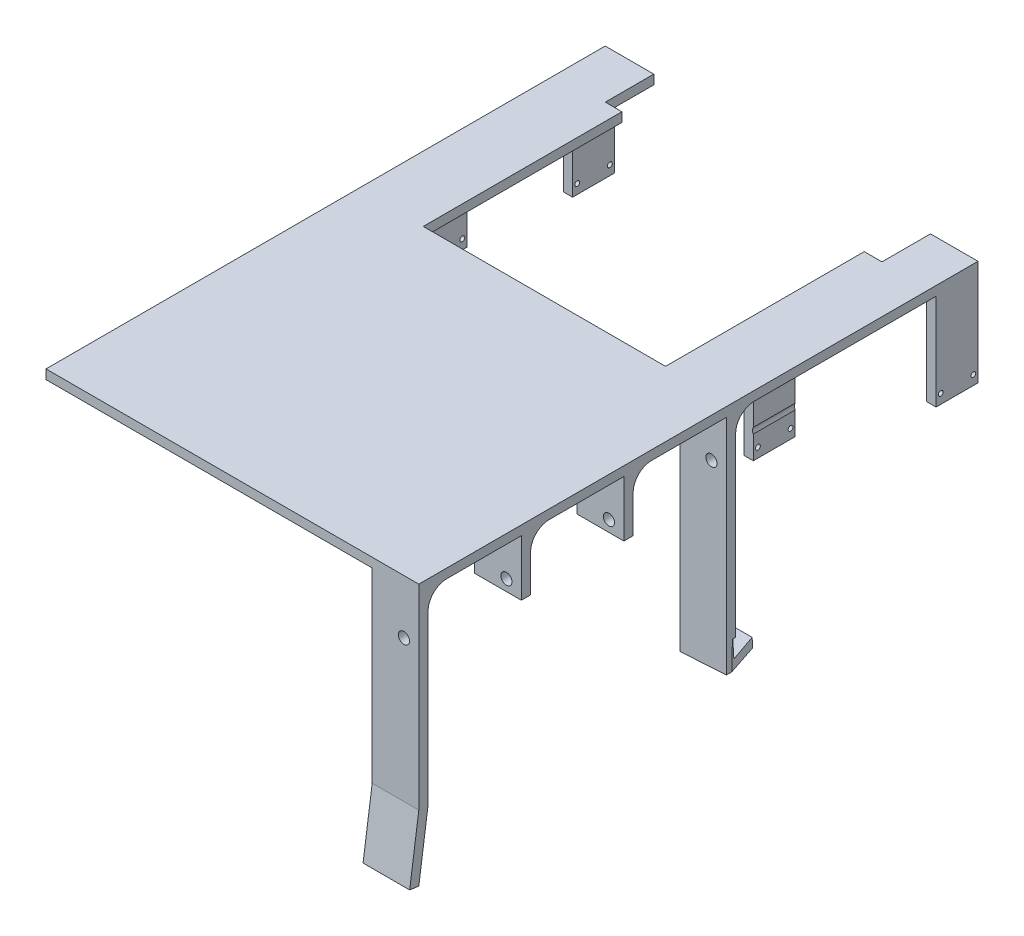
SolidWorks part; units mm, degrees
ref_plane "Front Plane" through (0, 0, 0) normal (0, 0, 1) x (1, 0, 0)
ref_plane "Top Plane" through (0, 0, 0) normal (0, 1, 0) x (1, 0, 0)
ref_plane "Right Plane" through (0, 0, 0) normal (1, 0, 0) x (0, 0, -1)
sketch "Sketch1" plane through (0, 0, 0) normal (0, 1, 0) x (1, 0, 0)
  line L0 (0, 0) -> (0, -300)
  line L1 (0, -300) -> (200, -300)
  line L2 (200, -300) -> (200, 0)
  line L3 (200, 0) -> (190, 0)
  line L4 (190, 0) -> (165, 0)
  line L5 (165, 0) -> (165, -132.6267)
  line L6 (165, -132.6267) -> (35, -132.6267)
  line L7 (35, -132.6267) -> (35, 0)
  line L8 (35, 0) -> (10, 0)
  line L9 (10, 0) -> (0, 0)
  line L10 (100, -300) -> (100, -132.6267) construction
  point P9 (100, -132.6267)
  point P12 (120, 0)
  dimension "D1" = 300
  dimension "D2" = 10
  dimension "D3" = 200
  dimension "D5" = 10
  dimension "D6" = 35
extrude "Boss-Extrude1" add sketch "Sketch1" along normal blind 5
sketch "Sketch2" plane through (0, 0, 0) normal (0, -1, 0) x (1, 0, 0)
  line L1 (8.3629, 110) -> (13.3629, 110)
  line L2 (8.3629, 110) -> (8.3629, 87.5)
  line L3 (8.3629, 87.5) -> (13.3629, 87.5)
  line L4 (13.3629, 110) -> (13.3629, 87.5)
  line L6 (189.4438, 110) -> (184.4438, 110)
  line L7 (189.4438, 110) -> (189.4438, 87.5)
  line L8 (189.4438, 87.5) -> (184.4438, 87.5)
  line L9 (184.4438, 110) -> (184.4438, 87.5)
  line L10 (0, 300) -> (200, 300) construction
  dimension "D1" = 5
  dimension "D2" = 22.5
  dimension "D3" = 5
  dimension "D4" = 190
  dimension "D5" = 22.5
extrude "Boss-Extrude2" add sketch "Sketch2" along normal blind 38
sketch "Sketch5" plane through (0, 0, 0) normal (0, -1, 0) x (1, 0, 0)
  line L0 (200, 300) -> (200, 0) construction
  line L1 (200, 295) -> (175, 295)
  line L2 (200, 295) -> (200, 300)
  line L3 (200, 300) -> (175, 300)
  line L4 (175, 295) -> (175, 300)
  line L5 (0, 300) -> (200, 300) construction
  line L6 (200, 240) -> (175, 240)
  line L7 (200, 240) -> (200, 245)
  line L8 (200, 245) -> (175, 245)
  line L9 (175, 240) -> (175, 245)
  line L10 (200, 185) -> (175, 185)
  line L11 (200, 185) -> (200, 190)
  line L12 (200, 190) -> (175, 190)
  line L13 (175, 185) -> (175, 190)
  line L14 (200, 130) -> (175, 130)
  line L15 (200, 130) -> (200, 135)
  line L16 (200, 135) -> (175, 135)
  line L17 (175, 130) -> (175, 135)
  dimension "D1" = 5
  dimension "D2" = 5
  dimension "D3" = 5
  dimension "D4" = 5
  dimension "D5" = 50
  dimension "D6" = 50
  dimension "D7" = 50
  dimension "D8" = 25
extrude "Boss-Extrude3" add sketch "Sketch5" along normal blind 30
fillet "Fillet3" radius 10 4 edges at (187.5, 0, 130) (187.5, 0, 185) (187.5, 0, 240) (187.5, 0, 295)
sketch "Sketch6" plane through (0, 0, 300) normal (0, 0, 1) x (1, 0, 0)
  line L0 (200, -30) -> (175, -30) construction
  line L1 (200, 5) -> (200, -30) construction
  circle A0 centre (192, -24) radius 3
  point P2 (0, 0)
  dimension "D1" = 6
  dimension "D2" = 6
  dimension "D3" = 8
extrude "Cut-Extrude4" cut sketch "Sketch6" against normal through all
sketch "Sketch7" plane through (0, 0, 0) normal (0, -1, 0) x (1, 0, 0)
  line L0 (0, 0) -> (0, 300) construction
  line L1 (0, 22.5) -> (5, 22.5)
  line L2 (0, 22.5) -> (0, 0)
  line L3 (0, 0) -> (5, 0)
  line L4 (5, 22.5) -> (5, 0)
  line L6 (200, 22.5) -> (195, 22.5)
  line L7 (200, 22.5) -> (200, 0)
  line L8 (200, 0) -> (195, 0)
  line L9 (195, 22.5) -> (195, 0)
  line L10 (200, 0) -> (165, 0) construction
  dimension "D1" = 5
  dimension "D2" = 5
  dimension "D3" = 22.5
  dimension "D4" = 22.5
extrude "Boss-Extrude4" add sketch "Sketch7" along normal blind 51.5
sketch "Sketch3" plane through (200, 0, 0) normal (1, 0, 0) x (0, 0, -1)
  line L4 (-87.5, 0) -> (-110, 0)
  line L5 (-87.5, -38) -> (-87.5, 0)
  line L6 (-110, -38) -> (-87.5, -38)
  line L7 (-110, 0) -> (-110, -38)
  line L9 (-87.5, -38) -> (-87.5, 0)
  line L10 (-110, -38) -> (-87.5, -38)
  line L11 (-110, 0) -> (-110, -38)
  line L13 (-87.5, 0) -> (-110, 0)
  circle A0 centre (-107.5, -32.9) radius 1.3 construction
  circle A1 centre (-90, -32.9) radius 1.3 construction
  circle A2 centre (-107.5, -32.9) radius 1.3
  circle A3 centre (-90, -32.9) radius 1.3
  circle A4 centre (-20, -46.4) radius 1.3 construction
  circle A5 centre (-2.5, -46.4) radius 1.3 construction
  circle A6 centre (-20, -46.4) radius 1.3
  circle A7 centre (-2.5, -46.4) radius 1.3
  dimension "D1" = 0
extrude "Cut-Extrude2" cut sketch "Sketch3" against normal through all contours A3 | A2 | A6 | A7
sketch "Sketch9" plane through (0, 0, 0) normal (0, -1, 0) x (1, 0, 0)
  line L0 (35, 0) -> (5, 0) construction
  line L1 (26.0812, 0) -> (174.514, 0)
  line L2 (26.0812, 0) -> (26.0812, 26.03)
  line L3 (26.0812, 26.03) -> (174.514, 26.03)
  line L4 (174.514, 0) -> (174.514, 26.03)
extrude "Cut-Extrude6" cut sketch "Sketch9" against normal blind 10
sketch "Sketch10" plane through (0, -30, 0) normal (0, -1, 0) x (1, 0, 0)
  line L1 (200, 295) -> (175, 295)
  line L2 (200, 295) -> (200, 300)
  line L3 (200, 300) -> (175, 300)
  line L4 (175, 295) -> (175, 300)
  line L5 (175, 130) -> (200, 130)
  line L6 (175, 130) -> (175, 135)
  line L7 (175, 135) -> (200, 135)
  line L8 (200, 130) -> (200, 135)
extrude "Boss-Extrude5" add sketch "Sketch10" along normal blind 70
sketch "Sketch11" plane through (200, 0, 0) normal (1, 0, 0) x (0, 0, -1)
  line L0 (-300, -100) -> (-304.9019, -134.6439)
  line L1 (-304.9019, -134.6439) -> (-300, -135.3374)
  line L2 (-300, -135.3374) -> (-295, -100)
  line L3 (-300, -100) -> (-295, -100)
extrude "Boss-Extrude6" add sketch "Sketch11" against normal blind 25
sketch "Sketch12" plane through (0, -100, 0) normal (0, -1, 0) x (1, 0, 0)
  line L1 (175, 130) -> (200, 130)
  line L2 (175, 130) -> (175, 135)
  line L3 (175, 135) -> (200, 135)
  line L4 (200, 130) -> (200, 135)
extrude "Boss-Extrude7" add sketch "Sketch12" along normal blind 19.72
sketch "Sketch13" plane through (0, 0, 130) normal (0, 0, -1) x (-1, 0, 0)
  line L0 (-200, -115.3141) -> (-200, -119.72)
  line L1 (-200, -119.72) -> (-200, -10) construction
  line L2 (-200, -119.72) -> (-175, -121.2619)
  line L3 (-175, -121.2619) -> (-175, -115.3141)
  line L4 (-175, -115.3141) -> (-200, -115.3141)
  line L5 (-175, -119.72) -> (-175, -10) construction
  line L8 (-88.7239, -126.5865) -> (-200, -119.7234) construction
extrude "Boss-Extrude8" add sketch "Sketch13" along normal blind 15 and the other way blind 5
sketch "Sketch14" plane through (8.1138, -131.5548, 0) normal (0.0616, -0.9981, 0) x (0.9981, 0.0616, 0)
  line L0 (186.3576, 115) -> (192.2508, 132.0374)
  line L1 (192.2508, 115) -> (167.2033, 115) construction
  line L2 (192.2508, 115) -> (192.2508, 135) construction
  line L3 (192.2508, 132.0374) -> (198.0152, 130.431)
  line L4 (198.0152, 130.431) -> (197.5151, 111.3666)
  line L5 (197.5151, 111.3666) -> (186.3576, 109.6075)
  line L6 (186.3576, 109.6075) -> (186.3576, 115)
extrude "Cut-Extrude7" cut sketch "Sketch14" against normal blind 15
